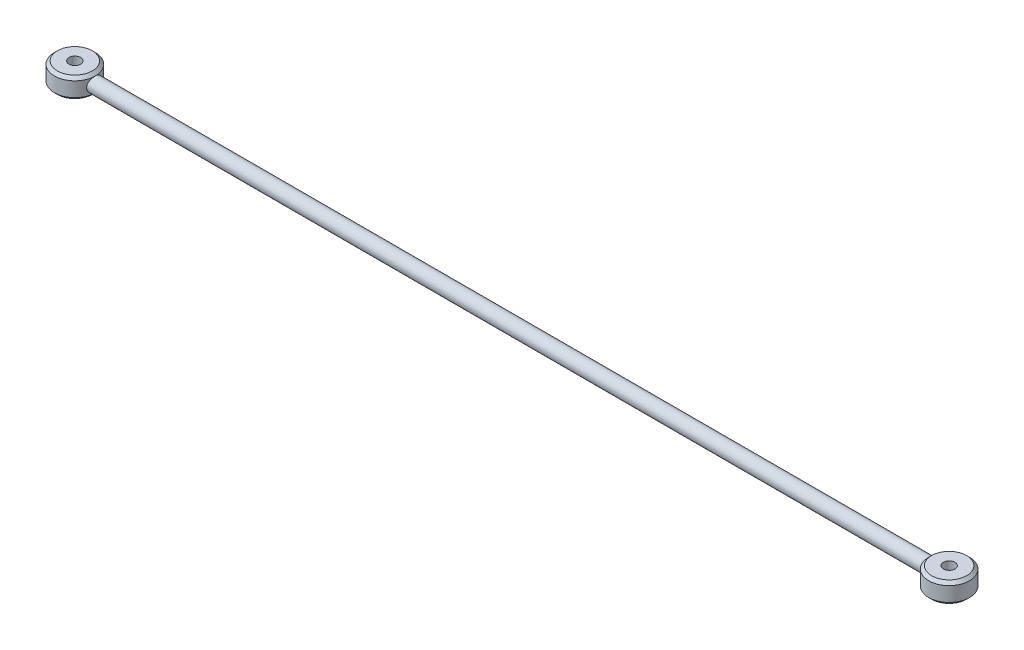
SolidWorks part; units mm, degrees
ref_plane "Front Plane" through (0, 0, 0) normal (0, 0, 1) x (1, 0, 0)
ref_plane "Top Plane" through (0, 0, 0) normal (0, 1, 0) x (1, 0, 0)
ref_plane "Right Plane" through (0, 0, 0) normal (1, 0, 0) x (0, 0, -1)
sketch "Sketch1" plane through (0, 0, 0) normal (0, 1, 0) x (1, 0, 0)
  line L0 (0, 0) -> (300, 0) construction
  circle A0 centre (0, 0) radius 7
  circle A1 centre (300, 0) radius 7
  circle A2 centre (0, 0) radius 2
  circle A3 centre (300, 0) radius 2
  dimension "D2" = 4
  dimension "D5" = 14
  dimension "D1" = 300
extrude "Boss-Extrude1" add sketch "Sketch1" along normal blind 3.5 and the other way blind 3.5
ref_plane "Plane1" through (150, 0, 0) normal (1, 0, 0) x (0, 0, -1)
ref_plane "Plane2" through (22.5, 0, 0) normal (1, 0, 0) x (0, 0, -1)
sketch "Sketch2" plane through (22.5, 0, 0) normal (1, 0, 0) x (0, 0, -1)
  circle A0 centre (0, 0) radius 2.5
  point P0 (0, 0)
  point P4 (0, 0)
  dimension "D2" = 5
extrude "Boss-Extrude2" add sketch "Sketch2" along normal up to surface and the other way up to surface up to face at (300, -3.5, 7) other way up to face at (0, -3.5, 7)
chamfer "Chamfer1" distance 1 angle 45 4 edges at (0, -3.5, 7) (0, 3.5, 7) (300, -3.5, 7) (300, 3.5, 7)
